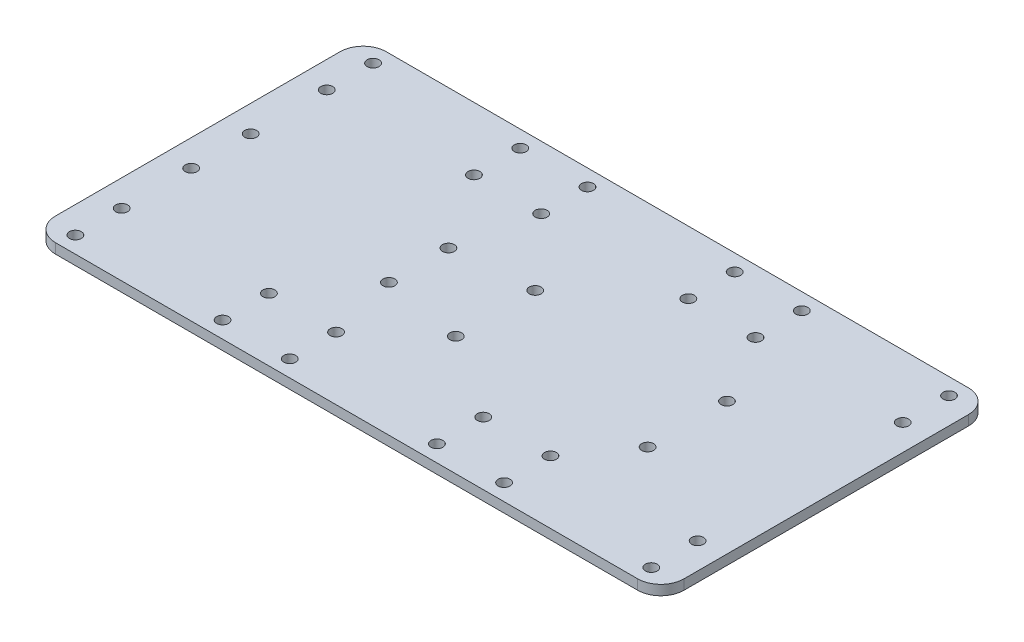
SolidWorks part; units mm, degrees
ref_plane "Front Plane" through (0, 0, 0) normal (0, 0, 1) x (1, 0, 0)
ref_plane "Top Plane" through (0, 0, 0) normal (0, 1, 0) x (1, 0, 0)
ref_plane "Right Plane" through (0, 0, 0) normal (1, 0, 0) x (0, 0, -1)
sketch "Sketch1" plane through (0, 0, 0) normal (0, 1, 0) x (1, 0, 0)
  line L1 (0, 0) -> (190, 0)
  line L2 (0, 0) -> (0, 100)
  line L3 (0, 100) -> (190, 100)
  line L4 (190, 0) -> (190, 100)
  dimension "D1" = 190
  dimension "D2" = 100
extrude "Boss-Extrude1" add sketch "Sketch1" along normal blind 3
hole_wizard "M3 Clearance Hole1" positions "Sketch3" profile "Sketch4" hole size "M3" standard "ANSI Metric" end condition through all
sketch "Sketch3" plane through (0, 3, 0) normal (0, 1, 0) x (1, 0, 0)
  line L1 (190, 100) -> (0, 100) construction
  line L2 (0, 100) -> (0, 0) construction
  line L3 (0, 50) -> (190, 50) construction
  line L4 (190, 0) -> (190, 100) construction
  line L5 (0, 0) -> (190, 0) construction
  point P0 (8, 95)
  point P2 (52.5, 95)
  point P4 (52.5, 81)
  point P6 (8, 81)
  point P32 (52.5, 19)
  point P33 (52.5, 5)
  point P34 (8, 19)
  point P35 (8, 5)
  point P45 (72.811, 95)
  point P46 (117.311, 95)
  point P47 (117.311, 81)
  point P48 (72.811, 81)
  point P49 (137.622, 95)
  point P50 (182.122, 95)
  point P51 (182.122, 81)
  point P52 (137.622, 81)
  point P54 (72.811, 19)
  point P55 (117.311, 19)
  point P56 (137.622, 19)
  point P57 (182.122, 19)
  point P58 (182.122, 5)
  point P59 (137.622, 5)
  point P60 (117.311, 5)
  point P61 (72.811, 5)
  point P64 (8, 58)
  point P66 (8, 40)
  point P68 (67.78, 58)
  point P70 (67.78, 40)
  point P72 (92, 60)
  point P74 (92, 36)
  point P76 (150, 36)
  point P78 (150, 60)
  dimension "D1" = 14
  dimension "D2" = 5
  dimension "D3" = 5
  dimension "D4" = 44.5
  dimension "D5" = 8
  dimension "D7" = 20.311
  dimension "D8" = 18
  dimension "D9" = 59.78
  dimension "D10" = 24
  dimension "D11" = 58
  dimension "D12" = 8
  dimension "D13" = 40
  dimension "D14" = 40
  dimension "D15" = 60
  dimension "D6" = 3
sketch "Sketch4" plane through (8, 3, -95) normal (1, 0, 0) x (0, 0, 1)
  line L0 (0, 0) -> (0, 3)
  line L1 (0, 3) -> (1.8, 3)
  line L2 (1.8, 3) -> (1.8, 0)
  line L5 (1.8, 0) -> (0, 0)
  line L11 (0, -6.35) -> (0, 107.95) construction
  dimension "Thru Hole Dia." = 3.6
  dimension "Thru Hole Depth" = 3
fillet "Fillet1" radius 7 4 edges at (190, 1.5, -100) (190, 1.5, 0) (0, 1.5, 0) (0, 1.5, -100)
